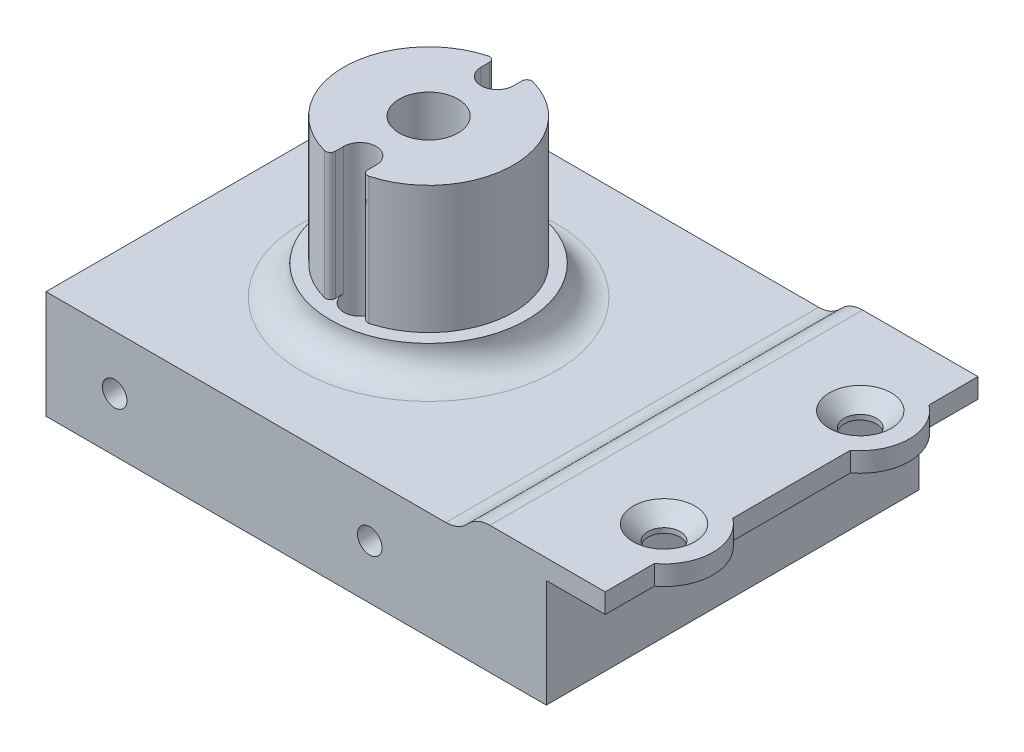
SolidWorks part; units mm, degrees
ref_plane "Спереди" through (0, 0, 0) normal (0, 0, 1) x (1, 0, 0)
ref_plane "Сверху" through (0, 0, 0) normal (0, 1, 0) x (1, 0, 0)
ref_plane "Справа" through (0, 0, 0) normal (1, 0, 0) x (0, 0, -1)
sketch "Эскиз6" plane through (0, 0, 0) normal (0, 1, 0) x (1, 0, 0)
  line L0 (-20, 0) -> (31, 0) construction
  line L1 (-20, -19) -> (31, -19)
  line L2 (-20, -19) -> (-20, 19)
  line L3 (-20, 19) -> (31, 19)
  line L4 (31, -19) -> (31, 19)
  line L5 (0, -19) -> (0, 19) construction
  dimension "D1" = 31
  dimension "D2" = 20
  dimension "D3" = 38
extrude "тело" add sketch "Эскиз6" along normal blind 11
sketch "Эскиз10" plane through (0, 11, 0) normal (0, 1, 0) x (1, 0, 0)
  circle A0 centre (0, 0) radius 10
  dimension "D1" = 20
extrude "основание оси" add sketch "Эскиз10" along normal blind 3
fillet "Скругление1" radius 3 1 edges at (0, 11, -10)
sketch "Эскиз13" plane through (0, 0, 19) normal (0, 0, 1) x (1, 0, 0)
  line L0 (31, 5.5) -> (-13, 5.5) construction
  line L1 (31, 11) -> (31, 0) construction
  line L2 (0, 0) -> (0, 11) construction
  line L3 (-20, 11) -> (31, 11) construction
  circle A0 centre (-13, 5.5) radius 1.25
  circle A1 centre (13, 5.5) radius 1.25
  dimension "D1" = 2.5
  dimension "D2" = 26
  dimension "D3" = 18
extrude "отверстия под шурупы" cut sketch "Эскиз13" against normal through all
sketch "Эскиз15" plane through (0, 14, 0) normal (0, 1, 0) x (1, 0, 0)
  circle A0 centre (0, 0) radius 8.65
  dimension "D1" = 17.3
extrude "ось" add sketch "Эскиз15" along normal blind 13
sketch "Эскиз16" plane through (0, 27, 0) normal (0, 1, 0) x (1, 0, 0)
  line L0 (-7, 1.65) -> (-8.4912, 1.65) construction
  line L1 (-7, -1.65) -> (-8.4912, -1.65) construction
  line L2 (-1.65, 7) -> (-1.65, 8.4912)
  line L3 (1.65, 7) -> (1.65, 8.4912)
  line L4 (7, 1.65) -> (8.4912, 1.65) construction
  line L5 (7, -1.65) -> (8.4912, -1.65) construction
  line L6 (1.65, -7) -> (1.65, -8.4912)
  line L8 (-1.65, -7) -> (-1.65, -8.4912)
  circle A0 centre (0, 0) radius 7 construction
  arc A1 (-1.65, 7) -> (1.65, 7) centre (0, 7) ccw
  arc A2 (7, 1.65) -> (7, -1.65) centre (7, 0) ccw construction
  arc A3 (1.65, -7) -> (-1.65, -7) centre (0, -7) ccw
  arc A4 (-7, -1.65) -> (-7, 1.65) centre (-7, 0) ccw construction
  arc A5 (-8.4912, 1.65) -> (-8.4912, -1.65) centre (0, 0) ccw construction
  circle A6 centre (0, 0) radius 8.65 construction
  arc A7 (1.65, 8.4912) -> (-1.65, 8.4912) centre (0, 0) ccw
  arc A8 (8.4912, -1.65) -> (8.4912, 1.65) centre (0, 0) ccw construction
  arc A9 (-1.65, -8.4912) -> (1.65, -8.4912) centre (0, 0) ccw
  dimension "D1" = 14
  dimension "D2" = 1.65
extrude "крепление к серве" cut sketch "Эскиз16" against normal up to surface (13 mm away) up to face at (0, 14, 8.65)
sketch "Эскиз26" plane through (0, 14, 0) normal (0, 1, 0) x (1, 0, 0)
  circle A0 centre (0, 7) radius 1.65
  circle A1 centre (0, -7) radius 1.65
  arc A2 (1.65, -7) -> (-1.65, -7) centre (0, -7) ccw construction
extrude "продолжение креплений" cut sketch "Эскиз26" against normal through all
chamfer "Фаска7" distance 2 angle 45 2 edges at (0, 0, -5.35) (0, 0, 8.65)
sketch "Эскиз17" plane through (0, 27, 0) normal (0, 1, 0) x (1, 0, 0)
  circle A0 centre (0, 0) radius 3
  dimension "D1" = 6
extrude "отверстие под болтик" cut sketch "Эскиз17" against normal through all
sketch "Эскиз24" [suppressed] plane through (0, 11, 0) normal (0, 1, 0) x (1, 0, 0)
  line L0 (31, 19) -> (-20, 19) construction
  line L1 (-15, 19) -> (15, 19)
  line L2 (-15, 19) -> (-15, -19)
  line L3 (-15, -19) -> (15, -19)
  line L4 (15, 19) -> (15, -19)
  line L5 (-20, -19) -> (31, -19) construction
  line L6 (0, 19) -> (0, -19) construction
  dimension "D1" = 30
extrude "крепление к арке" [suppressed] add sketch "Эскиз24" along normal blind 15
sketch "Эскиз27" [suppressed] plane through (-15, 0, 0) normal (-1, 0, 0) x (0, 0, 1)
  line L0 (0, 11) -> (0, 26) construction
  line L1 (-19, 11) -> (19, 11) construction
  line L2 (-19, 26) -> (19, 26) construction
  line L3 (-12.5, 18.5) -> (12.5, 18.5) construction
  circle A0 centre (-12.5, 18.5) radius 1.65
  circle A1 centre (12.5, 18.5) radius 1.65
  dimension "D2" = 3.3
  dimension "D1" = 25
  dimension "D3" = 7.5
extrude "отверстия под болты" [suppressed] cut sketch "Эскиз27" against normal through all
sketch "Эскиз19" plane through (0, 11, 0) normal (0, 1, 0) x (1, 0, 0)
  line L0 (-20, -19) -> (31, -19) construction
  line L1 (37, 19) -> (23, 19)
  line L2 (37, 19) -> (37, -19)
  line L3 (37, -19) -> (23, -19)
  line L4 (23, 19) -> (23, -19)
  line L5 (31, 19) -> (31, -19) construction
  line L6 (31, -19) -> (31, 19) construction
  dimension "D1" = 6
  dimension "D2" = 8
extrude "выступ прикрутиться к колену" add sketch "Эскиз19" along normal blind 2
sketch "Эскиз20" plane through (0, 13, 0) normal (0, 1, 0) x (1, 0, 0)
  line L0 (34, 19) -> (34, -19) construction
  line L1 (37, 19) -> (23, 19) construction
  line L2 (23, -19) -> (37, -19) construction
  line L3 (37, -19) -> (37, 19) construction
  line L4 (23, 0) -> (37, 0) construction
  line L5 (23, 19) -> (23, -19) construction
  circle A0 centre (34, 10) radius 1.65
  circle A1 centre (34, -10) radius 1.65
  dimension "D3" = 3.3
  dimension "D1" = 3
  dimension "D2" = 20
extrude "шурупы сверху" cut sketch "Эскиз20" against normal through all
sketch "Эскиз23" plane through (0, 13, 0) normal (0, 1, 0) x (1, 0, 0)
  circle A0 centre (34, 10) radius 5
  circle A1 centre (34, -10) radius 5
  circle A2 centre (34, 10) radius 1.65
  circle A3 centre (34, -10) radius 1.65
  circle A4 centre (34, -10) radius 1.65 construction
  circle A5 centre (34, 10) radius 1.65 construction
  dimension "D1" = 10
extrude "наплывы" add sketch "Эскиз23" against normal up to surface (2 mm away) up to face at (34, 11, 8.35)
chamfer "Фаска4" distance 1 angle 45 2 edges at (23, 13, 0) (23, 11, 0)
fillet "Скругление7" radius 3 2 edges at (22, 11, 0) (24, 13, 0)
chamfer "Фаска6" distance 1.5 angle 45 2 edges at (34, 13, 11.65) (34, 13, -8.35)
fillet "Скругление8" radius 0.5 4 edges at (-1.65, 20.5, -8.4912) (1.65, 20.5, -8.4912) (-1.65, 20.5, 8.4912) (1.65, 20.5, 8.4912)
